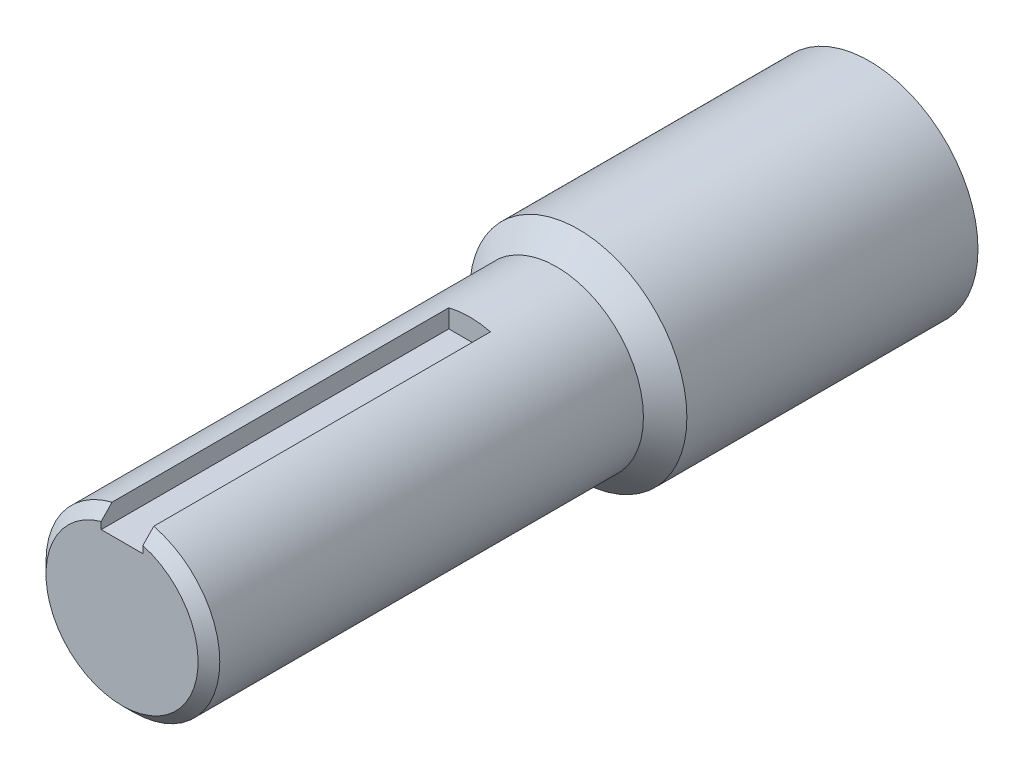
SolidWorks part; units mm, degrees
material "Plain Carbon Steel"
ref_plane "Front Plane" through (0, 0, 0) normal (0, 0, 1) x (1, 0, 0)
ref_plane "Top Plane" through (0, 0, 0) normal (0, 1, 0) x (1, 0, 0)
ref_plane "Right Plane" through (0, 0, 0) normal (1, 0, 0) x (0, 0, -1)
sketch "Sketch1" plane through (0, 0, 0) normal (0, 0, 1) x (1, 0, 0)
  circle A0 centre (0, 0) radius 7.9375
  dimension "D1" = 15.875
extrude "Boss-Extrude1" add sketch "Sketch1" along normal blind 3.81 and the other way blind 19.05
sketch "Sketch2" plane through (0, 0, 3.81) normal (0, 0, 1) x (1, 0, 0)
  circle A0 centre (0, 0) radius 6.35
  dimension "D1" = 12.7
extrude "Boss-Extrude2" add sketch "Sketch2" along normal blind 31.75
chamfer "Chamfer1" distance 1.5875 distance2 1.5875 1 edges at (7.9375, 0, 3.81)
chamfer "Chamfer2" distance 0.7937 angle 45 1 edges at (6.35, 0, 35.56)
sketch "Sketch3" plane through (0, 0, 35.56) normal (0, 0, 1) x (1, 0, 0)
  line L1 (-1.524, 4.826) -> (1.524, 4.826)
  line L2 (-1.524, 4.826) -> (-1.524, 6.35)
  line L3 (-1.524, 6.35) -> (1.524, 6.35)
  line L4 (1.524, 4.826) -> (1.524, 6.35)
  dimension "D1" = 1.524
  dimension "D2" = 3.048
  dimension "D3" = 1.524
  dimension "D4" = 6.35
extrude "Cut-Extrude1" cut sketch "Sketch3" against normal blind 25.4
